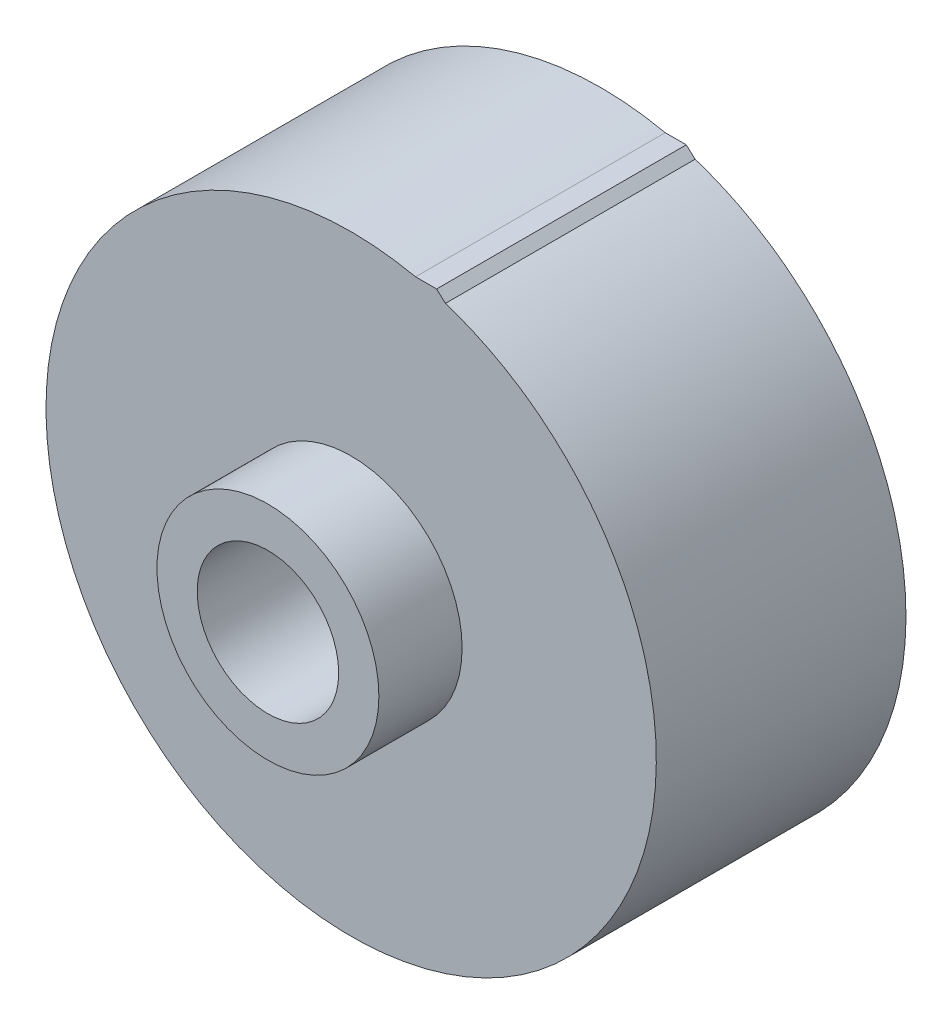
SolidWorks part; units mm, degrees
ref_plane "前视基准面" through (0, 0, 0) normal (0, 0, 1) x (1, 0, 0)
ref_plane "上视基准面" through (0, 0, 0) normal (0, 1, 0) x (1, 0, 0)
ref_plane "右视基准面" through (0, 0, 0) normal (1, 0, 0) x (0, 0, -1)
other "Configuration Table"
sketch "草图1" plane through (0, 0, 0) normal (0, 0, 1) x (1, 0, 0)
  circle A0 centre (0, 0) radius 8
  circle A1 centre (0, 0) radius 5.1
extrude "凸台-拉伸1" add sketch "草图1" along normal blind 24
extrude "凸台-拉伸2" add sketch "草图1<2>" along normal blind 24
sketch "草图1<2>" plane through (0, 0, 0) normal (0, 0, 1) x (1, 0, 0) same geometry as "草图1"
sketch "草图2" plane through (0, 0, 0) normal (0, 0, 1) x (1, 0, 0)
  circle A0 centre (0, 0) radius 22
  circle A1 centre (0, 0) radius 8
extrude "凸台-拉伸3" add sketch "草图2" along normal blind 18
sketch "草图3" plane through (0, 0, 0) normal (0, 0, 1) x (1, 0, 0)
  line L0 (17.4637, 0.7961) -> (22, 0)
  line L1 (22, 0) -> (21.9943, 0.501)
  line L2 (21.9943, 0.501) -> (22, 0)
  line L3 (22, 0) -> (21.9943, -0.501)
  line L4 (21.9943, -0.501) -> (21.9772, -1.0018)
  line L5 (21.9772, -1.0018) -> (17.4818, 0)
  arc A0 (17.4818, 0) -> (17.4637, 0.7961) centre (0, 0) ccw
  circle A1 centre (0, 0) radius 22 construction
sketch "草图4" plane through (0, 0, 0) normal (0, 0, 1) x (1, 0, 0)
  line L0 (16.38, 6.1601) -> (20.592, 7.7441)
  line L1 (20.592, 7.7441) -> (20.763, 7.2731)
  line L2 (20.763, 7.2731) -> (20.9232, 6.7984)
  line L3 (20.9232, 6.7984) -> (21.0726, 6.3201)
  line L4 (21.0726, 6.3201) -> (21.2111, 5.8385)
  line L5 (21.2111, 5.8385) -> (16.8725, 4.6443)
  arc A0 (16.8725, 4.6443) -> (16.38, 6.1601) centre (0, 0) ccw
  circle A1 centre (0, 0) radius 22 construction
extrude "凸台-拉伸5" add sketch "草图4" along normal blind 18
sketch "草图5" plane through (0, 0, 0) normal (0, 0, 1) x (1, 0, 0)
  line L0 (13.6747, 10.9203) -> (17.1911, 13.7284)
  line L1 (17.1911, 13.7284) -> (17.4993, 13.3333)
  line L2 (17.4993, 13.3333) -> (17.7984, 12.9313)
  line L3 (17.7984, 12.9313) -> (18.0883, 12.5226)
  line L4 (18.0883, 12.5226) -> (18.3688, 12.1074)
  line L5 (18.3688, 12.1074) -> (14.6115, 9.6309)
  arc A0 (14.6115, 9.6309) -> (13.6747, 10.9203) centre (0, 0) ccw
  arc A1 (20.592, 7.7441) -> (21.2111, 5.8385) centre (0, 0) ccw construction
extrude "凸台-拉伸6" add sketch "草图5" along normal blind 18
sketch "草图6" plane through (0, 0, 0) normal (0, 0, 1) x (1, 0, 0)
  line L0 (9.6309, 14.6115) -> (12.1074, 18.3688)
  line L1 (12.1074, 18.3688) -> (12.5226, 18.0883)
  line L2 (12.5226, 18.0883) -> (12.9313, 17.7984)
  line L3 (12.9313, 17.7984) -> (13.3333, 17.4993)
  line L4 (13.3333, 17.4993) -> (13.7284, 17.1911)
  line L5 (13.7284, 17.1911) -> (10.9203, 13.6747)
  arc A0 (10.9203, 13.6747) -> (9.6309, 14.6115) centre (0, 0) ccw
  arc A1 (17.1911, 13.7284) -> (21.2111, 5.8385) centre (0, 0) ccw construction
extrude "凸台-拉伸7" add sketch "草图6" along normal blind 18
sketch "草图7" plane through (0, 0, 0) normal (0, 0, 1) x (1, 0, 0)
  line L0 (4.6443, 16.8725) -> (4.6443, 21.5042)
  line L1 (4.6443, 21.5042) -> (6.1601, 21.5042)
  line L2 (6.1601, 21.5042) -> (6.7984, 20.9232)
  line L3 (6.7984, 20.9232) -> (7.2731, 20.763)
  line L4 (7.2731, 20.763) -> (7.7441, 20.592)
  line L5 (7.7441, 20.592) -> (6.1601, 16.38)
  arc A0 (6.1601, 16.38) -> (4.6443, 16.8725) centre (0, 0) ccw
  arc A1 (12.1074, 18.3688) -> (21.2111, 5.8385) centre (0, 0) ccw construction
extrude "凸台-拉伸8" add sketch "草图7" along normal blind 18
